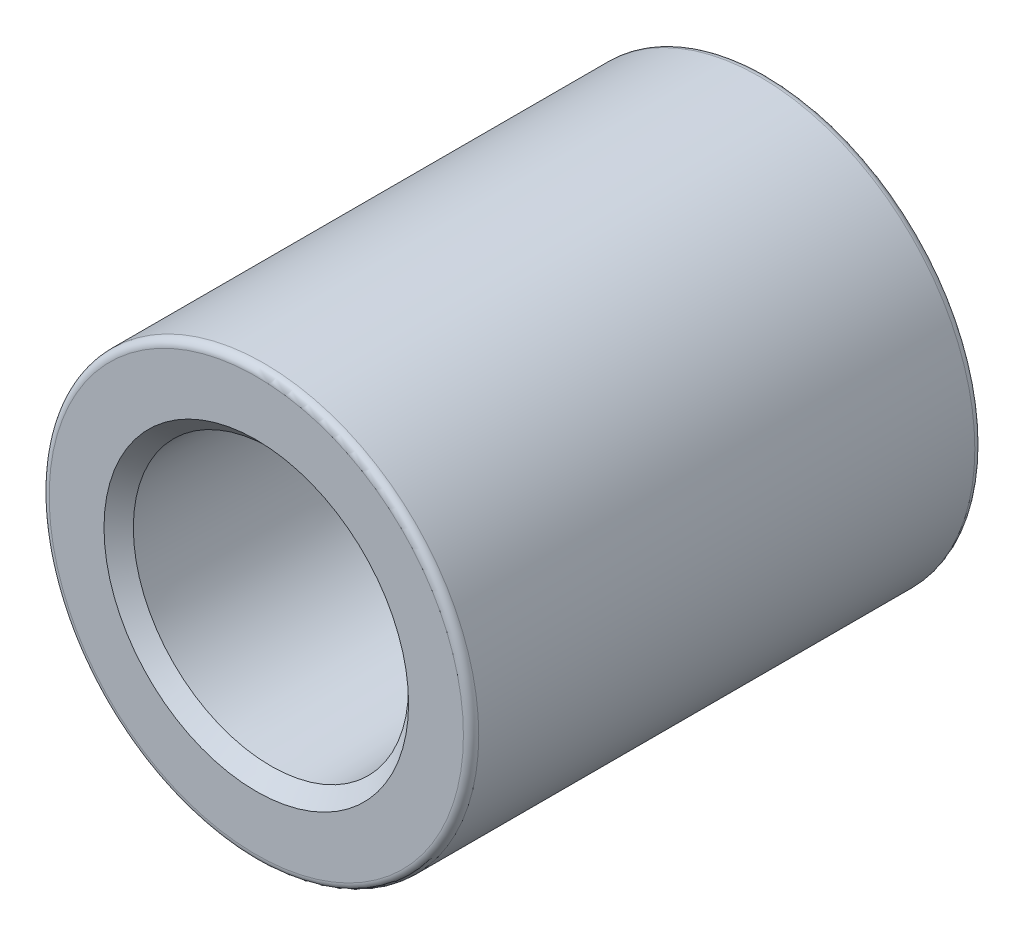
SolidWorks part; units mm, degrees
ref_plane "Front Plane" through (0, 0, 0) normal (0, 0, 1) x (1, 0, 0)
ref_plane "Top Plane" through (0, 0, 0) normal (0, 1, 0) x (1, 0, 0)
ref_plane "Right Plane" through (0, 0, 0) normal (1, 0, 0) x (0, 0, -1)
sketch "Sketch1" plane through (0, 0, 0) normal (0, 0, 1) x (1, 0, 0)
  circle A0 centre (0, 0) radius 10.668
  dimension "A" = 21.336
extrude "Extrude1" add sketch "Sketch1" along normal mid plane 25.4
sketch "Sketch2" plane through (0, 0, 12.7) normal (0, 0, 1) x (1, 0, 0)
  circle A0 centre (0, 0) radius 6.858
  dimension "pipe ID" = 13.716
extrude "Cut-Extrude1" cut sketch "Sketch2" against normal blind 10.2057 draft 1.783
sketch "Sketch3" plane through (0, 0, 2.4943) normal (0, 0, 1) x (1, 0, 0)
  circle A1 centre (0, 0) radius 6.5402
  circle A2 centre (0, 0) radius 6.5402 construction
curve "Helix/Spiral1" parameters "pitch"=1.4111
sketch "Sketch5" plane through (0, 0, 12.7) normal (0, 0, 1) x (1, 0, 0)
  line L0 (0, 7.5636) -> (0, 0) construction
  line L1 (0, 0) -> (-5.3482, 5.3482) construction
  circle A1 centre (0, 0) radius 7.5636
  circle A2 centre (0, 0) radius 6.858 construction
  dimension "D1" = 0.7056
  dimension "D2" = 45
sketch "Sketch4" plane through (0, 0, 0) normal (1, 0, 0) x (0, 0, -1)
  line L0 (-1.8769, 6.5402) -> (-2.4061, 5.6237)
  line L1 (-2.4061, 5.6237) -> (-2.5825, 5.6237)
  line L2 (-2.5825, 5.6237) -> (-3.1773, 6.654)
  line L3 (-1.8769, 6.5402) -> (-3.1116, 6.5402) construction
  line L4 (-1.8769, 6.5402) -> (-3.1773, 6.654)
  line L5 (-2.4943, 5.6237) -> (-2.4943, 6.5402) construction
  line L6 (-2.1415, 6.082) -> (-2.8471, 6.082) construction
  line L7 (-2.4943, 6.5402) -> (-2.4943, -6.5402) construction
  dimension "D1" = 5
  dimension "D2" = 60
  dimension "D3" = 0.1764
  dimension "D4" = 0.7056
sweep "Sweep1" [suppressed] add profiles "Sketch4" path "Helix/Spiral1"
sketch "Sketch6" plane through (0, 0, 12.7) normal (0, 0, 1) x (1, 0, 0)
  circle A1 centre (0, 0) radius 10.668
  circle A2 centre (0, 0) radius 10.668
  dimension "D1" = 0
extrude "Cut-Extrude2" [suppressed] cut sketch "Sketch6" along normal through all
extrude "Cut-Extrude3" cut sketch "Sketch5" against normal blind 3.175 draft 45
ref_axis "Axis1" through (0, 10.4775, 0) along (0, -1, 0)
pattern_circular "CirPattern1" count 2 over 360 about axis through (0, 10.4775, 0) along (0, -1, 0) of "Sweep1", "Cut-Extrude2", "Cut-Extrude3", "Cut-Extrude1"
sketch "Sketch7" plane through (0, 0, 0) normal (0, 0, 1) x (1, 0, 0)
  circle A3 centre (0, 0) radius 7.5636
  circle A4 centre (0, 0) radius 7.5636
  dimension "D2" = 0
extrude "Cut-Extrude4" [suppressed] cut sketch "Sketch7" along normal up to surface and the other way up to surface up to face at (6.5402, 0, 2.4943) other way up to face at (-6.5402, 0, -2.4943)
fillet "Fillet1" radius 0.381 2 edges at (10.668, 0, -12.7) (10.668, 0, 12.7)
equation "\"D3@Helix/Spiral1\" = \"E@Cut-Extrude1\"+ \"pitch@Helix/Spiral1\""
equation "\"D3@Sketch4\" = \"pitch@Helix/Spiral1\"*.125"
equation "\"D4@Sketch4\" = \"pitch@Helix/Spiral1\"*.5"
equation "\"D1@Sketch5\" = \"pitch@Helix/Spiral1\"*.5"
